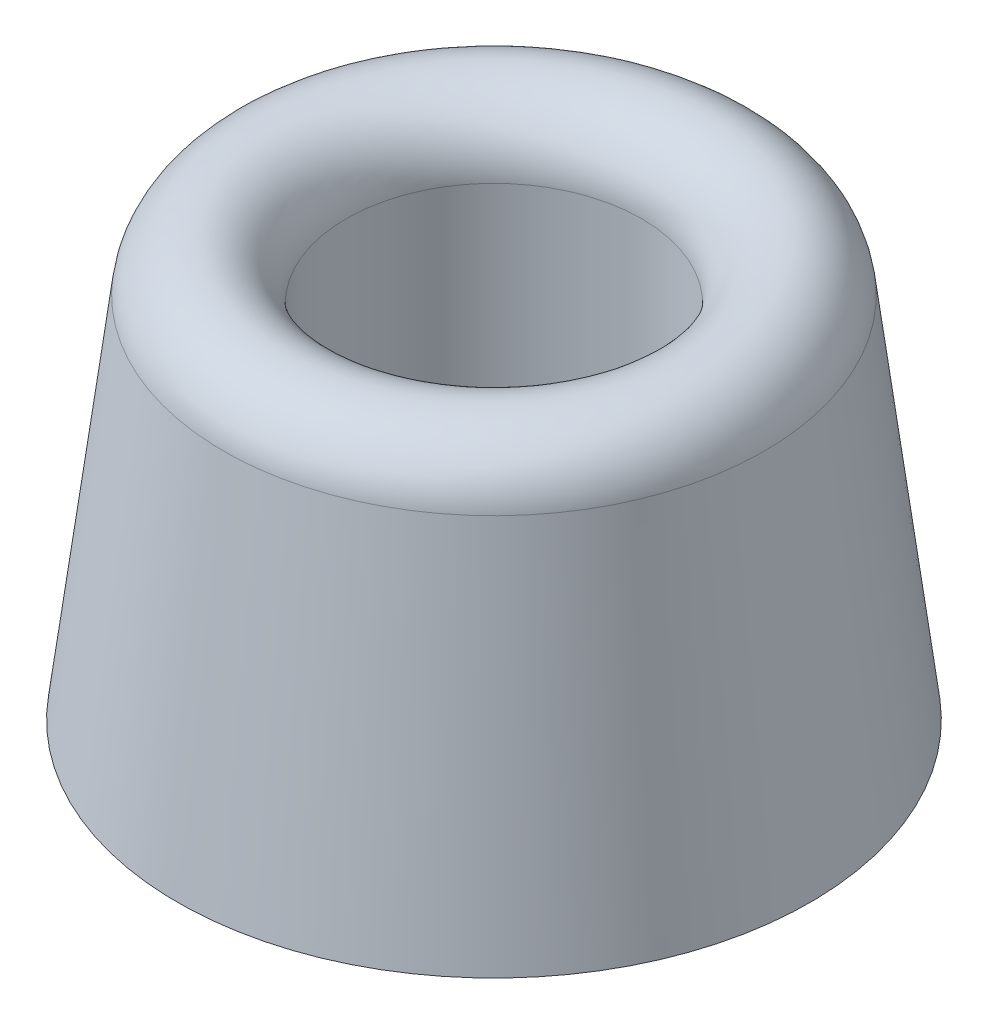
SolidWorks part; units mm, degrees
ref_plane "Front" through (0, 0, 0) normal (0, 0, 1) x (1, 0, 0)
ref_plane "Top" through (0, 0, 0) normal (0, 1, 0) x (1, 0, 0)
ref_plane "Right" through (0, 0, 0) normal (1, 0, 0) x (0, 0, -1)
sketch "Sketch1" plane through (0, 0, 0) normal (0, 0, 1) x (1, 0, 0)
  line L0 (11.9062, 0) -> (-11.9062, 0) construction
  line L1 (0, 0) -> (0, 15.875) construction
  line L2 (5.5562, 4.7625) -> (-5.5562, 4.7625) construction
  line L3 (2.7781, 0) -> (-2.7781, 0) construction
  point P7 (0, 4.7625)
  dimension "OD" = 23.8125
  dimension "Height" = 15.875
  dimension "Counterbore Dia" = 11.1125
  dimension "Mounting Surface Ht" = 4.7625
  dimension "Mounting Hole Dia" = 5.5562
sketch "Sketch2" plane through (0, 0, 0) normal (0, 0, 1) x (1, 0, 0)
  line L0 (-11.9062, 0) -> (-9.9219, 15.875) construction
  line L1 (-9.9219, 15.875) -> (-5.5563, 15.875) construction
  line L2 (-5.5563, 15.875) -> (-5.5562, 4.7625) construction
  line L3 (-5.5562, 4.7625) -> (-2.7781, 4.7625)
  line L4 (5.5562, 4.7625) -> (-5.5562, 4.7625) construction
  line L5 (-2.7781, 4.7625) -> (-2.7781, 0)
  line L6 (-2.7781, 0) -> (-11.9062, 0)
  line L7 (-9.9219, 15.875) -> (9.9219, 15.875) construction
  line L8 (-10.1758, 13.8439) -> (-11.9062, 0)
  line L9 (-5.5563, 13.5563) -> (-5.5562, 4.7625)
  arc A0 (-10.1758, 13.8439) -> (-5.5563, 13.5563) centre (-7.875, 13.5563) cw
  dimension "D1" = 19.8438
revolve "Revolve1" add sketch "Sketch2" angle 360 about L1
sketch "Sketch4" plane through (0, 0, 0) normal (0, 0, 1) x (1, 0, 0)
  line L0 (-5.5563, 13.5563) -> (-5.5563, 4.7625) construction
  line L1 (-2.7781, 4.7625) -> (-2.7781, 0) construction
  line L2 (2.7781, 0) -> (2.7781, 4.7625) construction
  line L3 (5.5563, 4.7625) -> (5.5563, 13.5563) construction
  line L4 (-5.5563, 13.5563) -> (-5.5563, 4.7625)
  line L5 (-2.7781, 4.7625) -> (-2.7781, 0)
  line L6 (2.7781, 0) -> (2.7781, 4.7625)
  line L7 (5.5563, 4.7625) -> (5.5563, 13.5563)
  line L8 (-5.5563, 4.7625) -> (-2.7781, 4.7625)
  line L9 (2.7781, 4.7625) -> (5.5563, 4.7625)
  arc A0 (-5.5563, 13.5563) -> (-7.875, 15.875) centre (-7.875, 13.5563) ccw construction
  arc A1 (-5.5563, 13.5563) -> (-7.875, 15.875) centre (-7.875, 13.5563) ccw
  arc A2 (7.875, 15.875) -> (5.5563, 13.5563) centre (7.875, 13.5563) ccw construction
  arc A3 (7.875, 15.875) -> (5.5563, 13.5563) centre (7.875, 13.5563) ccw
ref_plane "Contact Surface 1" through (0, 0, 0) normal (0, -1, 0) x (-1, 0, 0)
ref_axis "Center Axis1" through (0, -0.7937, 0) along (0, 1, 0)
equation "\"D1@Sketch2\"=\"OD@Sketch1\"/1.2"
